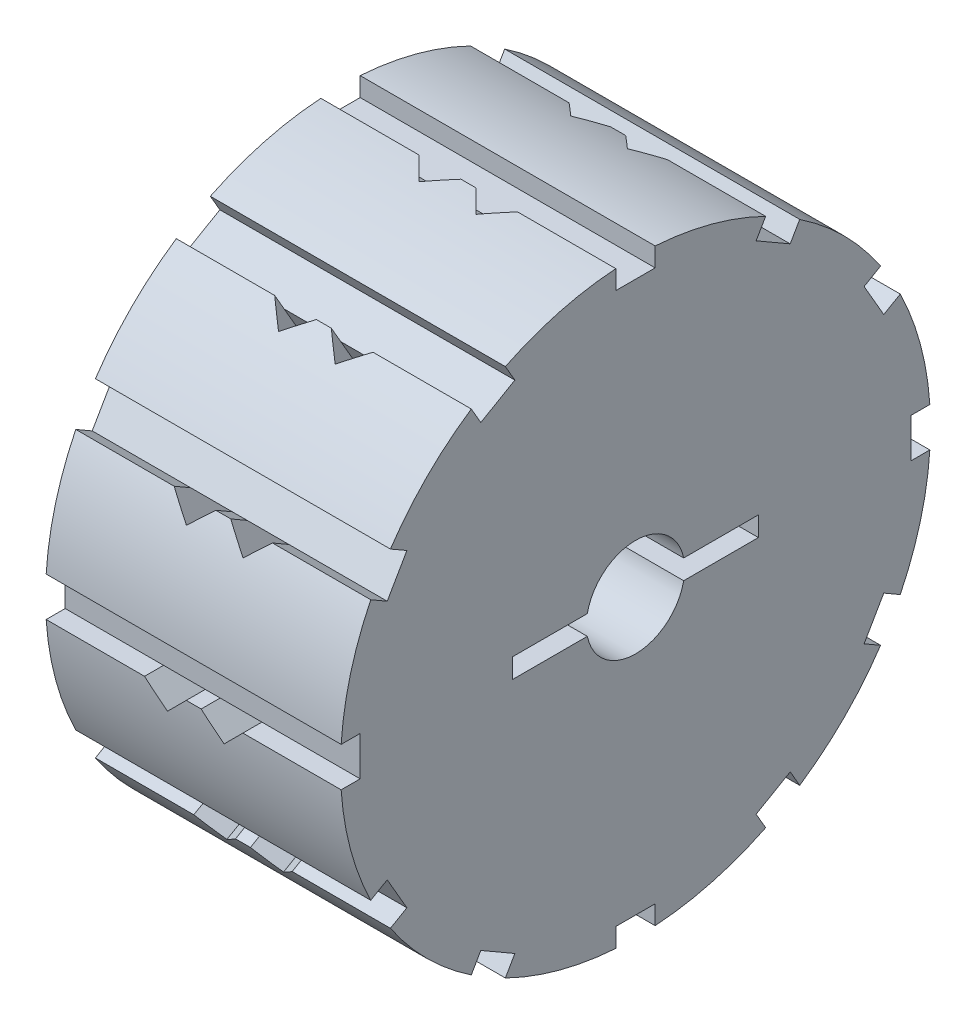
SolidWorks part; units mm, degrees
ref_plane "前视基准面" through (0, 0, 0) normal (0, 0, 1) x (1, 0, 0)
ref_plane "上视基准面" through (0, 0, 0) normal (0, 1, 0) x (1, 0, 0)
ref_plane "右视基准面" through (0, 0, 0) normal (1, 0, 0) x (0, 0, -1)
sketch "草图1" plane through (0, 0, 0) normal (1, 0, 0) x (0, 0, -1)
  circle A0 centre (0, 0) radius 30
  dimension "D1" = 60
extrude "凸台-拉伸1" add sketch "草图1" along normal blind 30
sketch "草图2" plane through (0, 0, 0) normal (1, 0, 0) x (0, 0, -1)
  line L1 (0, 30) -> (2, 30)
  line L2 (0, 30) -> (-2, 30)
  line L3 (-2, 30) -> (-2, 28)
  line L4 (2, 30) -> (2, 28)
  line L5 (-2, 28) -> (2, 28)
  dimension "D1" = 2
  dimension "D2" = 2
  dimension "D3" = 2
  dimension "D4" = 2
extrude "切除-拉伸1" cut sketch "草图2" along normal through all
sketch "草图3" plane through (0, 0, 0) normal (1, 0, 0) x (0, 0, -1)
  line L0 (4.899, -1) -> (12.5001, -1)
  line L2 (-4.899, 1) -> (-12.5, 1)
  line L3 (-12.5, 1) -> (-12.4999, -1)
  line L4 (-12.4999, -1) -> (-4.899, -1)
  line L5 (12.5001, -1) -> (12.5, 1)
  line L6 (12.5, 1) -> (4.899, 1)
  arc A0 (4.899, 1) -> (-4.899, 1) centre (0, 0) ccw
  arc A1 (-4.899, -1) -> (4.899, -1) centre (0, 0) ccw
  dimension "D1" = 10
  dimension "D5" = 25
  dimension "D6" = 2
  dimension "D7" = 2
extrude "切除-拉伸2" cut sketch "草图3" along normal through all
ref_axis "基准轴1" through (30, 0, 0) along (-1, 0, 0)
ref_plane "基准面1" through (0, 28, 0) normal (0, 1, 0) x (1, 0, 0)
sketch "草图4" plane through (0, 28, 0) normal (0, 1, 0) x (1, 0, 0)
  line L2 (14.2492, -2) -> (10.0066, -2)
  line L3 (15.7639, -2) -> (20.0066, -2)
  line L4 (10.0066, -2) -> (12.1279, -4.1213)
  line L5 (12.1279, -4.1213) -> (14.2492, -2)
  line L7 (20.0066, -2) -> (17.8852, -4.1213)
  line L8 (17.8852, -4.1213) -> (15.7639, -2)
  point P4 (15.0066, 0)
  dimension "D3" = 3
  dimension "D4" = 3
  dimension "D5" = 3
  dimension "D6" = 3
extrude "切除-拉伸3" cut sketch "草图4" against normal mid plane 18
pattern_circular "阵列(圆周)2" count 12 over 360 about axis through (30, 0, 0) along (-1, 0, 0) of "切除-拉伸1", "切除-拉伸3"
